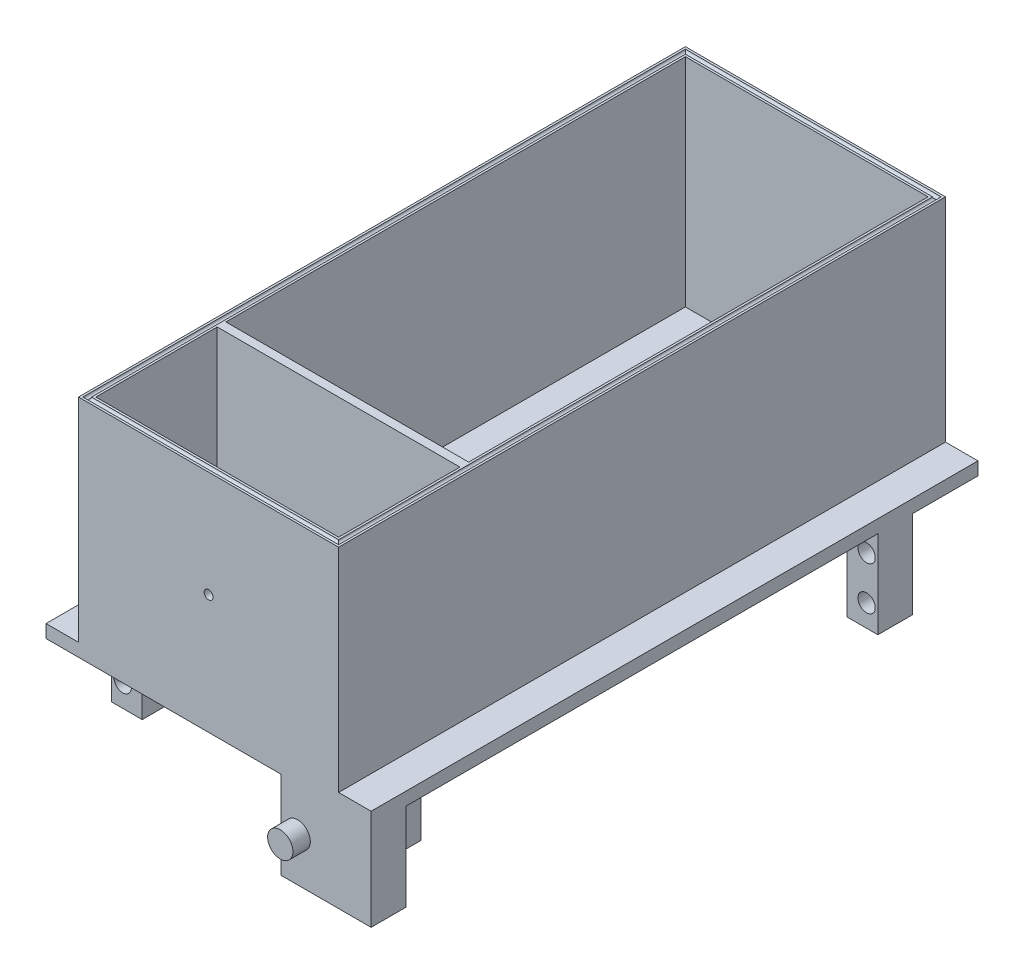
SolidWorks part; units mm, degrees
ref_plane "Front Plane" through (0, 0, 0) normal (0, 0, 1) x (1, 0, 0)
ref_plane "Top Plane" through (0, 0, 0) normal (0, 1, 0) x (1, 0, 0)
ref_plane "Right Plane" through (0, 0, 0) normal (1, 0, 0) x (0, 0, -1)
sketch "Sketch1" plane through (0, 0, 0) normal (0, 1, 0) x (1, 0, 0)
  line L1 (-30, 55) -> (30, 55)
  line L2 (-30, 55) -> (-30, -55)
  line L3 (-30, -55) -> (30, -55)
  line L4 (30, 55) -> (30, -55)
  line L5 (-30, 55) -> (30, -55) construction
  line L6 (-30, -55) -> (30, 55) construction
  point P0 (0, 0)
  dimension "D1" = 110
  dimension "D2" = 60
extrude "Boss-Extrude1" add sketch "Sketch1" along normal blind 2
sketch "Sketch2" plane through (0, 2, 0) normal (0, 1, 0) x (1, 0, 0)
  line L0 (-28, 53) -> (-28, -53)
  line L1 (-28, -53) -> (28, -53)
  line L2 (28, -53) -> (28, 53)
  line L3 (28, 53) -> (-28, 53)
  line L4 (30, -55) -> (30, 55)
  line L5 (30, 55) -> (-30, 55)
  line L6 (-30, 55) -> (-30, -55)
  line L7 (-30, -55) -> (30, -55)
  line L8 (30, -55) -> (30, 55)
  line L9 (30, 55) -> (-30, 55)
  line L10 (-30, 55) -> (-30, -55)
  line L11 (-30, -55) -> (30, -55)
  dimension "D1" = 0
  dimension "D2" = 2
extrude "Boss-Extrude2" add sketch "Sketch2" along normal blind 50
sketch "Sketch3" plane through (0, 0, 0) normal (0, 1, 0) x (1, 0, 0)
  line L0 (-30, -55) -> (30, -55) construction
  line L1 (-30, -55) -> (30, -55)
  line L2 (-30, -55) -> (-30, -85)
  line L3 (-30, -85) -> (30, -85)
  line L4 (30, -55) -> (30, -85)
  line L5 (30, -55) -> (30, 55) construction
  line L6 (-30, 55) -> (-30, -55) construction
  dimension "D2" = 30
extrude "Boss-Extrude3" add sketch "Sketch3" along normal blind 2
sketch "Sketch4" plane through (0, 2, 0) normal (0, 1, 0) x (1, 0, 0)
  line L4 (-28, -55) -> (-30, -55)
  line L8 (-28, -57) -> (-28, -83)
  line L9 (-28, -83) -> (28, -83)
  line L10 (28, -83) -> (28, -57)
  line L11 (28, -57) -> (-28, -57)
  line L12 (-28, -55) -> (-28, -83)
  line L13 (-28, -83) -> (28, -83)
  line L14 (28, -83) -> (28, -55)
  line L16 (-30, -55) -> (-30, -85)
  line L17 (-30, -85) -> (30, -85)
  line L18 (30, -85) -> (30, -55)
  line L19 (30, -55) -> (-30, -55)
  line L20 (-30, -55) -> (-30, -85)
  line L21 (-30, -85) -> (30, -85)
  line L22 (30, -85) -> (30, -55)
  line L23 (30, -55) -> (28, -55)
  dimension "D1" = 2
  dimension "D2" = 0
extrude "Boss-Extrude4" add sketch "Sketch4" along normal blind 50
sketch "Sketch5" plane through (0, 0, 55) normal (0, 0, 1) x (1, 0, 0)
  circle A0 centre (0, 15.8909) radius 2.4868
extrude "Cut-Extrude1" cut sketch "Sketch5" against normal blind 30
sketch "Sketch6" plane through (0, 52, 0) normal (0, 1, 0) x (1, 0, 0)
  line L4 (-29, 54) -> (-29, -84)
  line L6 (-29, 54) -> (-29, -84)
  line L8 (-29, -84) -> (29, -84)
  line L10 (-29, -84) -> (29, -84)
  line L11 (29, -84) -> (29, 54)
  line L12 (29, -84) -> (29, 54)
  line L22 (29, 54) -> (-29, 54)
  line L30 (29, 54) -> (-29, 54)
  dimension "D1" = 1
sweep "Cut-Sweep1" cut path "Sketch6" circular profile diameter 1 parameters "D3"=1
sketch "Sketch43" plane through (0, 0, 0) normal (0, -1, 0) x (1, 0, 0)
  line L11 (30, -55) -> (37.5, -55)
  line L12 (37.5, -55) -> (37.5, 85)
  line L13 (37.5, 85) -> (30, 85)
  line L14 (-30, -55) -> (-37.5, -55)
  line L15 (-37.5, -55) -> (-37.5, 85)
  line L16 (-37.5, 85) -> (-30, 85)
  line L18 (-30, 55) -> (-30, -55)
  line L19 (-30, 55) -> (-30, 85)
  line L21 (30, -55) -> (30, 85)
  dimension "D1" = 7.5
  dimension "D2" = 7.5
extrude "Boss-Extrude7" add sketch "Sketch43" against normal blind 3 contours L13 L21 L11 L12 | L16 L19 L18 L14 L15
sketch "Sketch55" plane through (0, 0, 0) normal (0, -1, 0) x (1, 0, 0)
  line L0 (-37.5, 85) -> (37.5, 85) construction
  line L1 (-37.5, 69.9) -> (-30.4, 69.9)
  line L2 (-37.5, 69.9) -> (-37.5, 61.9)
  line L3 (-37.5, 61.9) -> (-30.4, 61.9)
  line L4 (-30.4, 69.9) -> (-30.4, 61.9)
  line L6 (9.6, 69.9) -> (9.6, 61.9)
  line L9 (37.5, -55) -> (-37.5, -55) construction
  line L10 (37.5, -39.9) -> (30.4, -39.9)
  line L11 (37.5, -39.9) -> (37.5, -31.9)
  line L12 (37.5, -31.9) -> (30.4, -31.9)
  line L13 (30.4, -39.9) -> (30.4, -31.9)
  line L15 (-9.6, -39.9) -> (-9.6, -31.9)
  line L20 (-9.6, -39.9) -> (-16.7, -39.9)
  line L21 (-16.7, -39.9) -> (-16.7, -55)
  line L22 (-16.7, -55) -> (-37.5, -55)
  line L23 (-37.5, -55) -> (-37.5, -47)
  line L24 (-37.5, -55) -> (-37.5, 85) construction
  line L25 (-37.5, -47) -> (-24.7, -47)
  line L26 (-24.7, -47) -> (-24.7, -31.9)
  line L27 (-24.7, -31.9) -> (-9.6, -31.9)
  line L28 (9.6, 69.9) -> (16.7, 69.9)
  line L29 (16.7, 69.9) -> (16.7, 85)
  line L30 (16.7, 85) -> (37.5, 85)
  line L33 (37.5, 85) -> (37.5, 77)
  line L34 (37.5, -55) -> (37.5, 85) construction
  line L35 (37.5, 77) -> (25.882, 77)
  line L37 (25.882, 77) -> (25.882, 61.9)
  line L38 (25.882, 61.9) -> (9.6, 61.9)
  dimension "D1" = 7.1
  dimension "D2" = 8
  dimension "D3" = 8
  dimension "D4" = 15.1
  dimension "D5" = 40
  dimension "D6" = 8
  dimension "D7" = 7.1
  dimension "D8" = 8
  dimension "D9" = 7.1
  dimension "D10" = 40
  dimension "D11" = 8
  dimension "D12" = 8
  dimension "D13" = 15.1
  dimension "D14" = 7.1
  dimension "D15" = 8
extrude "Boss-Extrude10" add sketch "Sketch55" along normal blind 20.2
sketch "Sketch56" plane through (0, 0, 85) normal (0, 0, 1) x (1, 0, 0)
  line L1 (-10.4, 0) -> (-10.4, -17.0658) construction
  line L4 (-34.9, -15.1) -> (-34.9, -5.1) construction
  line L6 (-37.5, 0) -> (16.7, 0) construction
  circle A0 centre (-34.9, -15.1) radius 2
  circle A1 centre (-34.9, -5.1) radius 2
  circle A2 centre (14.1, -15.1) radius 2
  circle A3 centre (14.1, -5.1) radius 2
  dimension "D1" = 4
  dimension "D2" = 4
  dimension "D3" = 10
  dimension "D4" = 49
  dimension "D5" = 24.5
extrude "Cut-Extrude3" cut sketch "Sketch56" against normal blind 46.2
sketch "Sketch59" plane through (0, 0, -55) normal (0, 0, -1) x (-1, 0, 0)
  line L0 (-34.9, -5.1) -> (-34.9, -15.1) construction
  line L1 (-10.4, 0) -> (-10.4, -20.2) construction
  line L5 (-37.5, 0) -> (16.7, 0) construction
  circle A0 centre (-34.9, -15.1) radius 2
  circle A1 centre (-34.9, -5.1) radius 2
  circle A2 centre (14.1, -5.1) radius 2
  circle A3 centre (14.1, -15.1) radius 2
  dimension "D2" = 4
  dimension "D3" = 4
  dimension "D1" = 10
  dimension "D4" = 24.5
extrude "Cut-Extrude4" cut sketch "Sketch59" against normal blind 49.2
sketch "Sketch60" plane through (0, 0, -55) normal (0, 0, -1) x (-1, 0, 0)
  line L0 (37.5, 3) -> (37.5, -20.2) construction
  line L1 (30, 3) -> (-30, 3) construction
  line L2 (-37.5, 0) -> (16.7, 0) construction
  circle A0 centre (20.55, -10.1) radius 2.925
  dimension "D1" = 5.85
  dimension "D2" = 16.95
  dimension "D3" = 10.1
extrude "Boss-Extrude11" add sketch "Sketch60" along normal blind 4
sketch "Sketch61" plane through (0, 0, 85) normal (0, 0, 1) x (1, 0, 0)
  line L0 (30, 3) -> (-30, 3) construction
  line L1 (-37.5, 0) -> (16.7, 0) construction
  line L4 (37.5, 3) -> (37.5, -20.2) construction
  circle A0 centre (20.55, -10.1) radius 2.925
  dimension "D1" = 5.85
  dimension "D2" = 16.95
  dimension "D3" = 10.1
extrude "Boss-Extrude12" add sketch "Sketch61" along normal blind 4
sketch "Sketch62" plane through (0, 0, 85) normal (0, 0, 1) x (1, 0, 0)
  line L0 (0, 0) -> (0, 27.5) construction
  line L1 (0, 27.5) -> (-30, 27.5) construction
  line L2 (-30, 52) -> (-30, 3) construction
  circle A0 centre (0, 27.5) radius 1.025
  dimension "D1" = 2.05
extrude "Cut-Extrude5" cut sketch "Sketch62" against normal blind 10
